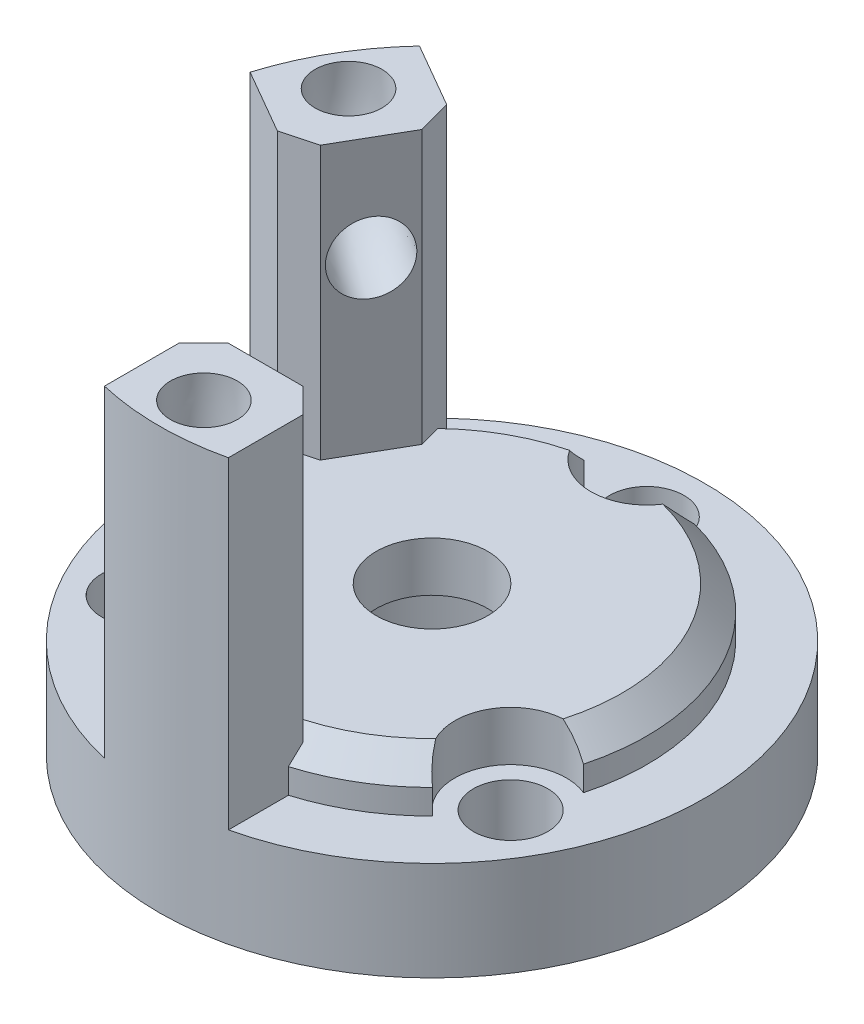
SolidWorks part; units mm, degrees
ref_plane "前视基准面" through (0, 0, 0) normal (0, 0, 1) x (1, 0, 0)
ref_plane "上视基准面" through (0, 0, 0) normal (0, 1, 0) x (1, 0, 0)
ref_plane "右视基准面" through (0, 0, 0) normal (1, 0, 0) x (0, 0, -1)
other "Configuration Table"
sketch "草图1" plane through (0, 0, 0) normal (0, 1, 0) x (1, 0, 0)
  circle A0 centre (0, 0) radius 11
  circle A1 centre (0, 0) radius 6.25
  dimension "D1" = 22
  dimension "D2" = 12.5
extrude "凸台-拉伸1" add sketch "草图1" along normal blind 4
sketch "草图2" plane through (0, 4, 0) normal (0, 1, 0) x (1, 0, 0)
  circle A0 centre (0, 0) radius 8.6603 construction
  circle A1 centre (0, 8.6603) radius 1.5
  circle A2 centre (7.5, -4.3301) radius 1.5
  circle A3 centre (-7.5, -4.3301) radius 1.5
  point P12 (0, 0)
  dimension "D1" = 15
  dimension "D2" = 3
  dimension "D3" = 3
extrude "切除-拉伸1" cut sketch "草图2" against normal up to next
sketch "草图3" plane through (0, 4, 0) normal (0, 1, 0) x (1, 0, 0)
  line L0 (-7.5, -4.3301) -> (0, 0) construction
  line L1 (0, 0) -> (7.5, -4.3301) construction
  line L2 (0, 0) -> (0, 8.6603) construction
  circle A0 centre (0, 8.6603) radius 2.25
  circle A1 centre (-7.5, -4.3301) radius 2.25
  circle A2 centre (7.5, -4.3301) radius 2.25
  circle A3 centre (0, 0) radius 8.6603
  circle A4 centre (0, 0) radius 6.25 construction
  circle A7 centre (0, 0) radius 2.25
  circle M5 centre (0, 0) radius 6.25
  dimension "D1" = 4.5
  dimension "D2" = 4.5
  dimension "D3" = 120
extrude "凸台-拉伸2" add sketch "草图3" along normal blind 2 contours A2 A3 A0 A1 M5 | A7 M5 region at (0, 4, -6.386) region at (-6.0732, 4, 0)
chamfer "倒角1" distance 1 angle 45 3 edges at (-7.5, 6, -4.3301) (7.5, 6, -4.3301) (0, 6, 8.6603)
sketch "草图4" plane through (0, 4, 0) normal (0, 1, 0) x (1, 0, 0)
  line L0 (-10.527, 3.191) -> (-7.0629, 1.191)
  line L1 (-7.0629, 1.191) -> (-4.5629, 5.5211)
  line L2 (-4.5629, 5.5211) -> (-8.027, 7.5211)
  line L3 (0, 0) -> (-5.8129, 3.3561) construction
  line L4 (0, 0) -> (0, 4.5) construction
  circle A0 centre (0, 0) radius 11 construction
  circle A1 centre (0, 0) radius 11
  circle A3 centre (0, 0) radius 4.5
  circle M6 centre (0, 0) radius 11
  arc M13 (-8.3623, -2.2519) -> (-2.2309, 8.368) centre (0, 0) cw
  dimension "D2" = 9
  dimension "D1" = 4
  dimension "D3" = 60
  dimension "D4" = 5
extrude "凸台-拉伸3" add sketch "草图4" along normal blind 13 contours L2 L0 M13 M6 | L1 L2 L0 M13 region at (-8.4182, 4, -4.8603) region at (-6.6065, 4, -3.8143)
ref_plane "基准面1" through (0, 0, 0) normal (-0.5, 0, 0.866) x (0.866, 0, 0.5)
sketch "草图8" plane through (0, 0, 0) normal (-0.5, 0, 0.866) x (0.866, 0, 0.5)
  line L2 (-5, 11.4644) -> (-5, 10.6456) construction
  line L3 (-5, 14.5) -> (-5, 13.5356) construction
  line L4 (-5, 13.5356) -> (-5, 11.4644) construction
  line L5 (-5, 12.5) -> (-3.5493, 12.5) construction
  line L6 (-10.7121, 17) -> (-6.7121, 17) construction
  line L7 (-11, 17) -> (-6.7121, 17) construction
  line L13 (-10.7121, 17) -> (-11, 17) construction
  line L14 (-10.7121, 17) -> (-11, 17) construction
  line L15 (-6.7121, 17) -> (-6.7121, 6) construction
  spline S1 degree 3 poles (-9.2, 17) (-9.2, 16.0117) (-9.0176, 13.2971) (-6.198, 12.5) (-5, 12.5) knots 0 0 0 0 0.445305 1 1 1 1
  dimension "D1" = 1.8
sweep "切除-扫描1" cut path "草图8" circular profile diameter 2.7 parameters "D3"=2.7
ref_axis "基准轴1" through (0, 23.0332, 0) along (0, -1, 0)
ref_plane "基准面2" through (0, 0, 0) normal (0.5, 0, 0.866) x (0.866, 0, -0.5)
mirror "镜向1" about plane through (0, 0, 0) normal (0.5, 0, 0.866) of "凸台-拉伸3"
chamfer "倒角2" distance 1 angle 45 4 edges at (-7.0629, 11.5, -1.191) (-4.5629, 11.5, -5.5211) (2.5, 11.5, 6.7121) (-2.5, 11.5, 6.7121)
ref_plane "基准面3" through (0, 0, 0) normal (-1, 0, 0) x (0, 0, 1)
sketch "草图11" plane through (0, 0, 0) normal (-1, 0, 0) x (0, 0, 1)
  line L0 (5, 10.6456) -> (5, 8.3544) construction
  line L1 (5, 9.5) -> (3.6772, 9.5) construction
  line L2 (7.7121, 17) -> (7.7121, 5.553) construction
  line L3 (6.7121, 6) -> (6.7121, 17) construction
  line L4 (6.7121, 17) -> (11, 17) construction
  spline S0 degree 3 poles (9.2, 17) (9.2, 15.8424) (9.4808, 14.0818) (9.1209, 11.6021) (8.1149, 10.0632) (6.5245, 9.453) (5.5376, 9.5) (5, 9.5) knots 0 0 0 0 0.340104 0.512478 0.728023 0.832977 1 1 1 1
  dimension "D1" = 1.8
sweep "切除-扫描2" cut path "草图11" circular profile diameter 2.7 parameters "D3"=2.7
